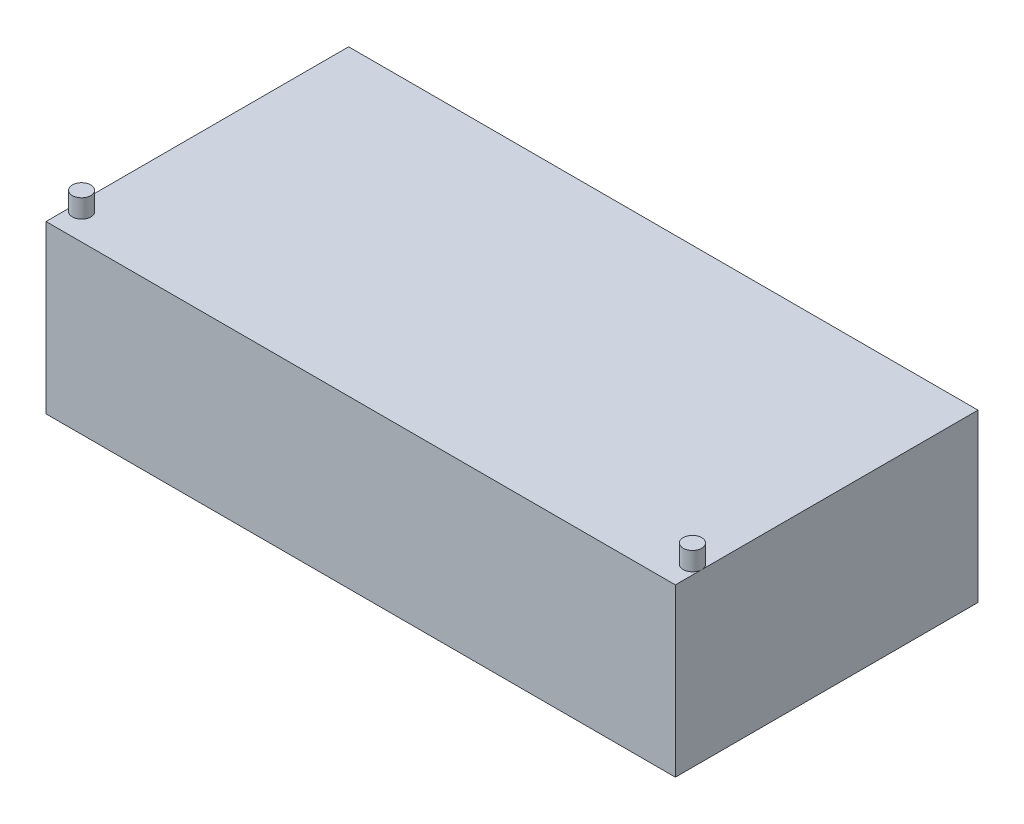
SolidWorks part; units mm, degrees
material "Custom Plastic"
ref_plane "Front Plane" through (0, 0, 0) normal (0, 0, 1) x (1, 0, 0)
ref_plane "Top Plane" through (0, 0, 0) normal (0, 1, 0) x (1, 0, 0)
ref_plane "Right Plane" through (0, 0, 0) normal (1, 0, 0) x (0, 0, -1)
sketch "Sketch1" plane through (0, 0, 0) normal (0, 1, 0) x (1, 0, 0)
  line L1 (-170, 81.75) -> (170, 81.75)
  line L2 (-170, 81.75) -> (-170, -81.75)
  line L3 (-170, -81.75) -> (170, -81.75)
  line L4 (170, 81.75) -> (170, -81.75)
  line L5 (-170, 81.75) -> (170, -81.75) construction
  line L6 (-170, -81.75) -> (170, 81.75) construction
  point P0 (0, 0)
  dimension "D1" = 163.5
  dimension "D2" = 340
extrude "Boss-Extrude1" add sketch "Sketch1" along normal blind 90
sketch "Sketch2" plane through (0, 90, 0) normal (0, 1, 0) x (1, 0, 0)
  circle A0 centre (-165, -67.5) radius 5
  circle A1 centre (165, -67.5) radius 5
extrude "Boss-Extrude2" add sketch "Sketch2" along normal blind 10
